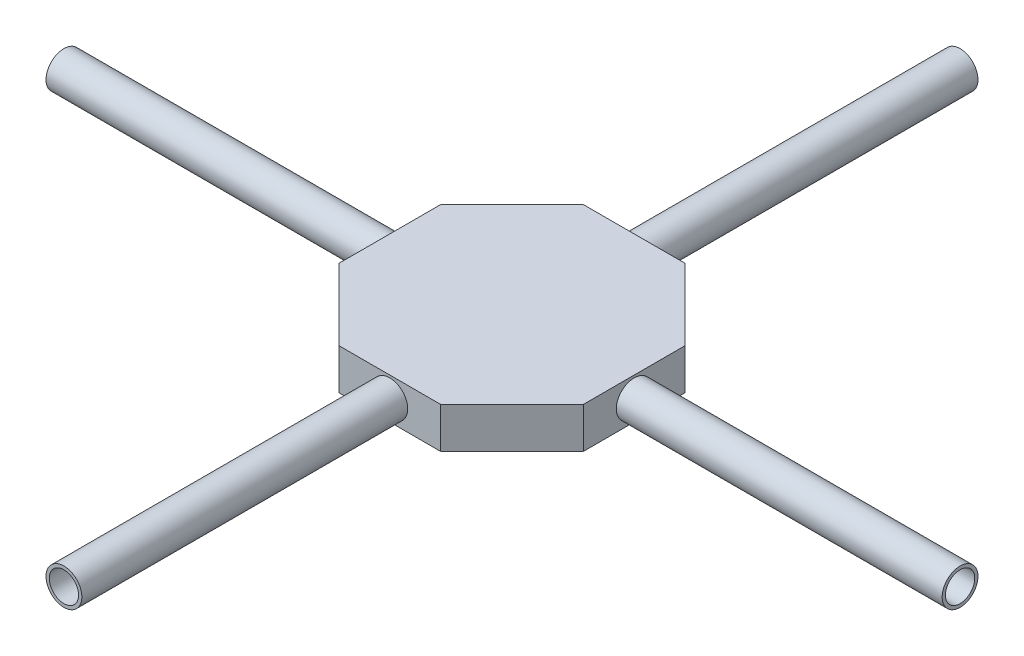
SolidWorks part; units mm, degrees
ref_plane "Front Plane" through (0, 0, 0) normal (0, 0, 1) x (1, 0, 0)
ref_plane "Top Plane" through (0, 0, 0) normal (0, 1, 0) x (1, 0, 0)
ref_plane "Right Plane" through (0, 0, 0) normal (1, 0, 0) x (0, 0, -1)
sketch "Sketch1" plane through (0, 0, 0) normal (0, 1, 0) x (1, 0, 0)
  line L0 (-75, 31.066) -> (-75, -31.066)
  line L7 (75, -31.066) -> (75, 31.066)
  line L8 (75, 31.066) -> (31.066, 75)
  line L9 (31.066, 75) -> (-31.066, 75)
  line L10 (-31.066, 75) -> (-75, 31.066)
  line L11 (-75, -31.066) -> (-31.066, -75)
  line L12 (-31.066, -75) -> (31.066, -75)
  line L13 (31.066, -75) -> (75, -31.066)
  line L14 (0, 0) -> (93.4101, 0) construction
  circle A0 centre (0, 0) radius 75 construction
  point P9 (0, 0)
  dimension "D1" = 150
extrude "Boss-Extrude1" add sketch "Sketch1" along normal blind 25
sketch "Sketch2" plane through (-75, 0, 0) normal (-1, 0, 0) x (0, 0, 1)
  line L0 (-31.066, 12.5) -> (31.066, 12.5) construction
  line L1 (-31.066, 25) -> (-31.066, 0) construction
  line L2 (31.066, 25) -> (31.066, 0) construction
  circle A0 centre (0, 12.5) radius 9
  circle A1 centre (0, 12.5) radius 11
  dimension "D1" = 18
  dimension "D2" = 22
extrude "Boss-Extrude2" add sketch "Sketch2" along normal blind 200
sketch "Sketch3" plane through (0, 0, 0) normal (1, 0, 0) x (0, 0, -1)
  line L0 (0, 0) -> (0, 25) construction
  line L1 (-31.066, 25) -> (31.066, 25) construction
ref_axis "Axis1" through (0, 0, 0) along (0, 1, 0)
pattern_circular "CirPattern1" count 4 every 90 about axis through (0, 0, 0) along (0, 1, 0) of "Boss-Extrude2"
